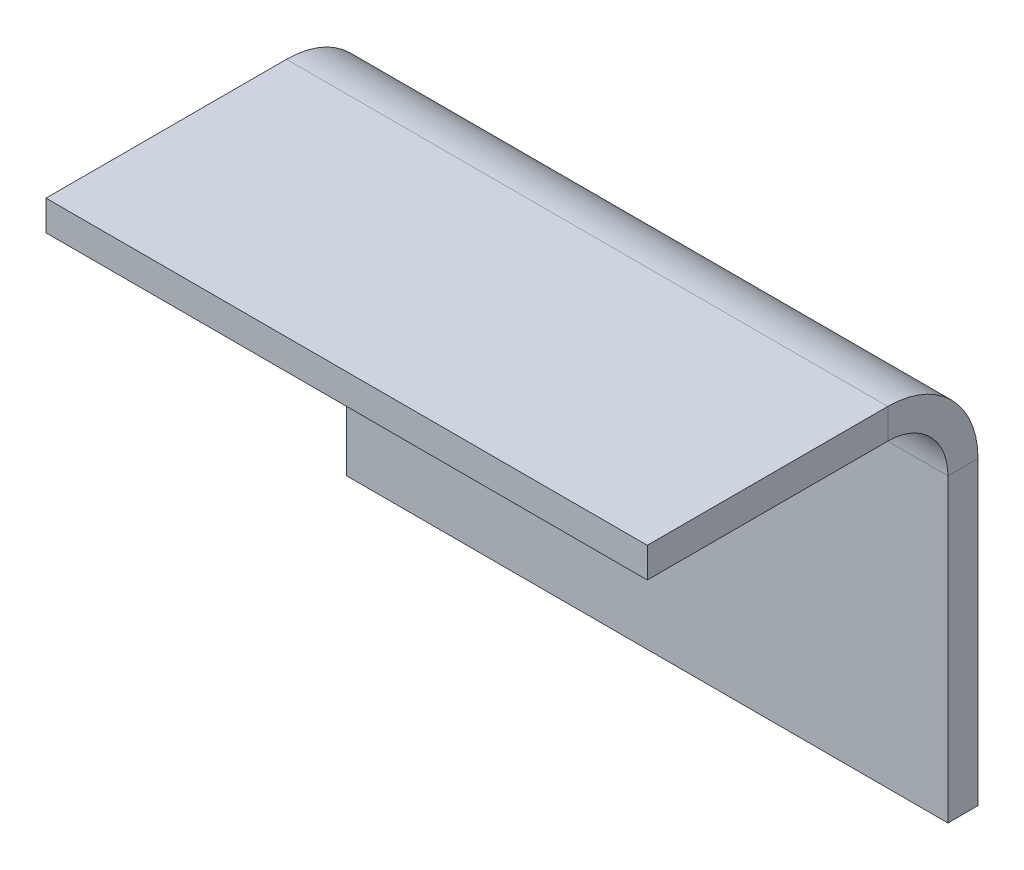
SolidWorks part; units mm, degrees
note: The reader was unsure of these and kept them because the rebuilt part matched: flange length of "EdgeFlange".
ref_plane "前视基准面" through (0, 0, 0) normal (0, 0, 1) x (1, 0, 0)
ref_plane "上视基准面" through (0, 0, 0) normal (0, 1, 0) x (1, 0, 0)
ref_plane "右视基准面" through (0, 0, 0) normal (1, 0, 0) x (0, 0, -1)
other "Configuration Table"
sketch "草图1" plane through (0, 0, 0) normal (0, 0, 1) x (1, 0, 0)
  line L1 (0, 0) -> (20, 0)
  line L2 (0, 0) -> (0, 10)
  line L3 (0, 10) -> (20, 10)
  line L4 (20, 0) -> (20, 10)
base flange "BasePlate" sketch "草图1" thickness 1 reverse thickness direction no parameters "D1"=2
sketch "草图9" plane through (0, 10, 0) normal (0, 1, 0) x (-1, 0, 0)
  line L0 (-20, 0) -> (0, 0) construction
  line L1 (-20, 0) -> (0, 0)
  line L2 (-20, 0) -> (-20, 10)
  line L3 (-20, 10) -> (-18, 10)
  line L4 (-18, 10) -> (-2, 10)
  line L5 (-2, 10) -> (0, 10)
  line L6 (0, 0) -> (0, 10)
edge flange "EdgeFlange" sketch "草图9" flange angle 90 flange length 10 flange position bend outside bend radius 2 thickness 1 relief rectangular parameters "D6"=10
bend "边线折弯1" bend radius 2 bend angle 90 parameters "D5"=1
sketch "折弯-线1" plane through (0, 0, 0) normal (0, 1, 0) x (1, 0, 0)
sketch "边界框1" plane through (0, 0, 0) normal (0, 1, 0) x (1, 0, 0)
sheet metal parameters "钣金6" thickness 1 parameters "D1"=2
flat pattern "平板型式6" [suppressed]
sketch "折弯-线2" plane through (0, 0, 0) normal (0, 1, 0) x (1, 0, 0)
sketch "边界框2" [suppressed] plane through (0, 0, 0) normal (0, 1, 0) x (1, 0, 0)
sheet metal parameters "钣金7" thickness 1 parameters "D1"=2
flat pattern "平板型式6" [suppressed]
sketch "折弯-线2" plane through (0, 0, 0) normal (0, 1, 0) x (1, 0, 0)
sketch "边界框2" [suppressed] plane through (0, 0, 0) normal (0, 1, 0) x (1, 0, 0)
bend of the flat pattern "展平-<边线折弯1>1"
